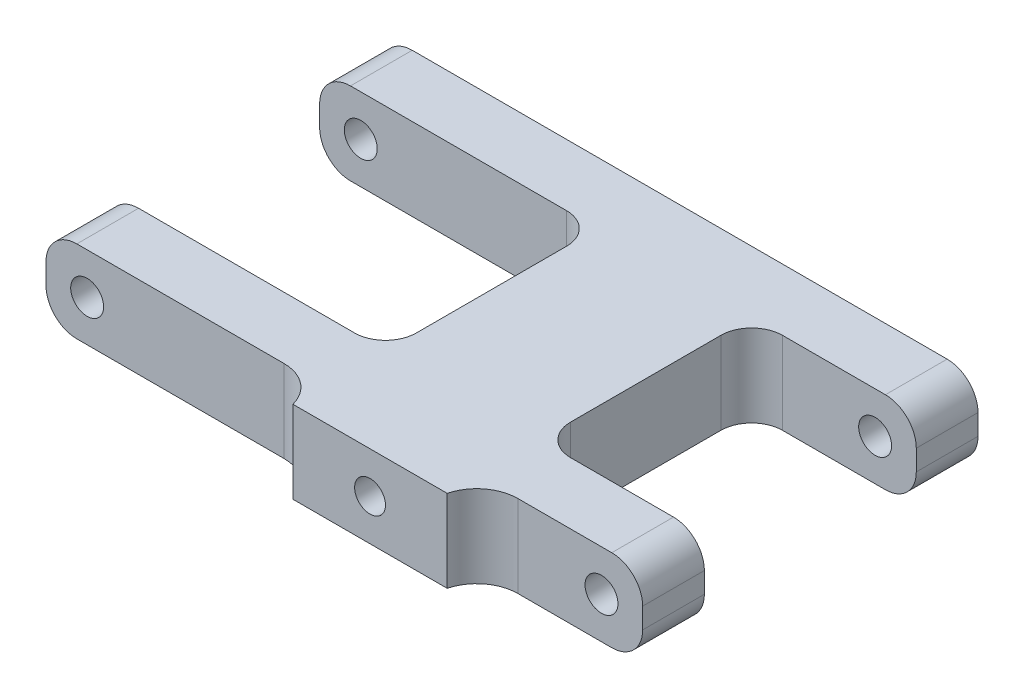
SolidWorks part; units mm, degrees
ref_plane "Front" through (0, 0, 0) normal (0, 0, 1) x (1, 0, 0)
ref_plane "Top" through (0, 0, 0) normal (0, 1, 0) x (1, 0, 0)
ref_plane "Right" through (0, 0, 0) normal (1, 0, 0) x (0, 0, -1)
sketch "Sketch1" plane through (0, 0, 0) normal (0, 1, 0) x (1, 0, 0)
  line L1 (0, 0) -> (58, 0)
  line L2 (0, 0) -> (0, -32.6)
  line L3 (0, -32.6) -> (58, -32.6)
  line L4 (58, 0) -> (58, -32.6)
  dimension "D1" = 32.6
  dimension "D2" = 58
extrude "Boss-Extrude1" add sketch "Sketch1" along normal blind 8
sketch "Sketch2" plane through (58, 0, 0) normal (1, 0, 0) x (0, 0, -1)
  line L0 (-32.6, 8) -> (0, 8) construction
  line L1 (-26.6, 8) -> (-6, 8)
  line L2 (-26.6, 8) -> (-26.6, 0)
  line L3 (-26.6, 0) -> (-6, 0)
  line L4 (-6, 8) -> (-6, 0)
  line L5 (-32.6, 0) -> (0, 0) construction
  line L6 (-32.6, 8) -> (-32.6, 0) construction
  line L7 (0, 8) -> (0, 0) construction
  dimension "D1" = 6
  dimension "D2" = 6
extrude "Cut-Extrude1" cut sketch "Sketch2" against normal blind 16
sketch "Sketch3" plane through (0, 0, 0) normal (-1, 0, 0) x (0, 0, 1)
  line L0 (0, 8) -> (32.6, 8) construction
  line L1 (6, 8) -> (26.6, 8)
  line L2 (6, 8) -> (6, 0)
  line L3 (6, 0) -> (26.6, 0)
  line L4 (26.6, 8) -> (26.6, 0)
  line L5 (0, 0) -> (32.6, 0) construction
  line L6 (32.6, 8) -> (32.6, 0) construction
  line L7 (0, 8) -> (0, 0) construction
  dimension "D1" = 6
  dimension "D2" = 6
extrude "Cut-Extrude2" cut sketch "Sketch3" against normal blind 27
sketch "Sketch5" plane through (0, 0, 32.6) normal (0, 0, 1) x (1, 0, 0)
  line L0 (0, 8) -> (58, 8) construction
  line L1 (0, 8) -> (0, 0) construction
  circle A0 centre (4, 4) radius 1.6
  circle A1 centre (54, 4) radius 1.6
  dimension "D1" = 3.2
  dimension "D2" = 4
  dimension "D3" = 4
  dimension "D4" = 2
extrude "Cut-Extrude4" cut sketch "Sketch5" against normal through all
fillet "Fillet1" radius 3 8 edges at (0, 0, 29.6) (0, 8, 29.6) (0, 0, 3) (0, 8, 3) (58, 8, 3) (58, 0, 3) (58, 0, 29.6) (58, 8, 29.6)
fillet "Fillet2" radius 3 4 edges at (42, 4, 26.6) (42, 4, 6) (27, 4, 26.6) (27, 4, 6)
sketch "Sketch7" plane through (0, 0, 32.6) normal (0, 0, 1) x (1, 0, 0)
  line L0 (3, 8) -> (55, 8) construction
  line L1 (27, 8) -> (42, 8)
  line L2 (27, 8) -> (27, 0)
  line L3 (27, 0) -> (42, 0)
  line L4 (42, 8) -> (42, 0)
  line L5 (3, 0) -> (55, 0) construction
  line L6 (58, 5) -> (58, 3) construction
  line L7 (0, 5) -> (0, 3) construction
  dimension "D1" = 16
  dimension "D2" = 27
extrude "Boss-Extrude2" add sketch "Sketch7" along normal blind 3
sketch "Sketch6" plane through (0, 0, 32.6) normal (0, 0, 1) x (1, 0, 0)
  line L0 (3, 0) -> (27, 0) construction
  line L2 (0, 5) -> (0, 3) construction
  circle A0 centre (34.5, 4) radius 1.5
  dimension "D1" = 3
  dimension "D2" = 4
  dimension "D3" = 34.5
extrude "Cut-Extrude5" cut sketch "Sketch6" against normal blind 15 and the other way blind 3
fillet "Fillet3" radius 4 2 edges at (42, 4, 32.6) (27, 4, 32.6)
